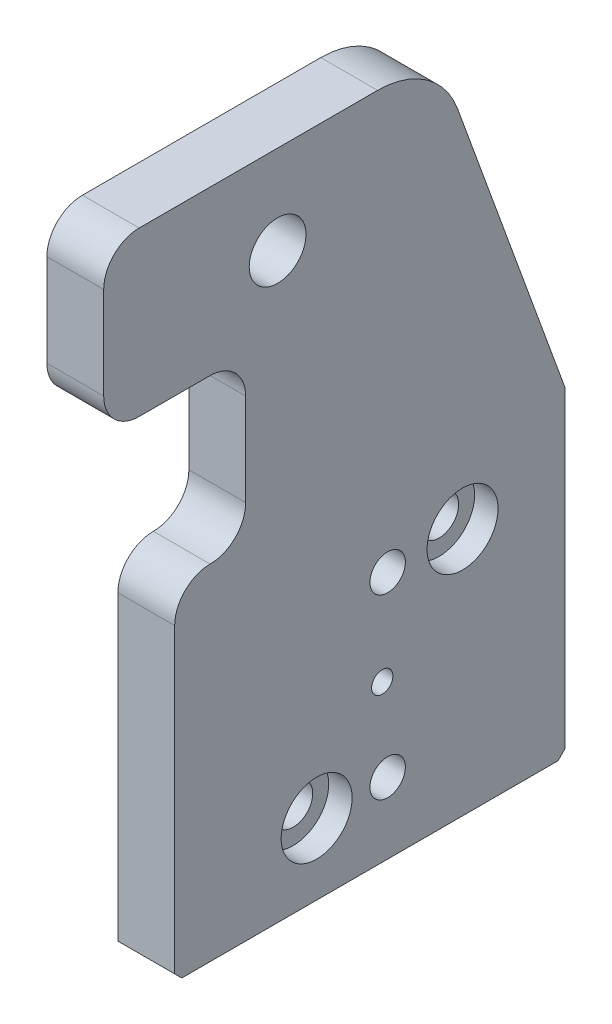
SolidWorks part; units mm, degrees
ref_plane "Front Plane" through (0, 0, 0) normal (0, 0, 1) x (1, 0, 0)
ref_plane "Top Plane" through (0, 0, 0) normal (0, 1, 0) x (1, 0, 0)
ref_plane "Right Plane" through (0, 0, 0) normal (1, 0, 0) x (0, 0, -1)
sketch "Sketch1" plane through (0, 0, 0) normal (1, 0, 0) x (0, 0, -1)
  line L0 (65, 45) -> (46.9835, 94.5)
  line L1 (0, 0) -> (65, 0)
  line L2 (0, 0) -> (0, 94.5)
  line L3 (0, 94.5) -> (65, 94.5)
  line L4 (65, 0) -> (65, 94.5)
  line L5 (0, 0) -> (65, 94.5) construction
  line L6 (0, 94.5) -> (65, 0) construction
  line L7 (0, 71.5) -> (20, 71.5)
  line L8 (20, 71.5) -> (20, 48.5)
  line L9 (20, 48.5) -> (10, 48.5)
  line L10 (10, 48.5) -> (10, 0)
  point P4 (32.5, 47.25)
  dimension "D1" = 65
  dimension "D2" = 94.5
  dimension "D3" = 45
  dimension "D4" = 20
  dimension "D5" = 55
  dimension "D6" = 48.5
extrude "Boss-Extrude1" add sketch "Sketch1" along normal blind 8 contours L9 L10 L1 L4 L0 L3 L2 L7 L8 region at (0, 45.4776, -34.9988)
fillet "Fillet1" radius 12 1 edges at (4, 94.5, -46.9835)
fillet "Fillet2" radius 5 1 edges at (4, 94.5, 0)
fillet "Fillet3" radius 5 4 edges at (4, 48.5, -10) (4, 48.5, -20) (4, 71.5, -20) (4, 71.5, 0)
chamfer "Chamfer2" distance 1 angle 45 2 edges at (4, 0, -10) (4, 0, -65)
sketch "Sketch5" plane through (0, 0, 0) normal (1, 0, 0) x (0, 0, -1)
  line L0 (0, 82) -> (24.5, 82) construction
  line L1 (0, 76.5) -> (0, 89.5) construction
  line L2 (24.5, 82) -> (24.5, 94.5) construction
  line L3 (5, 94.5) -> (38.581, 94.5) construction
  dimension "D1" = 12.5
  dimension "D2" = 24.5
sketch "Sketch8" plane through (0, 0, 0) normal (1, 0, 0) x (0, 0, -1)
  line L0 (10, 10.0011) -> (65, 10.0011) construction
  line L1 (10, 43.5) -> (10, 1) construction
  line L2 (65, 1) -> (65, 45) construction
  line L3 (11, 0) -> (64, 0) construction
  line L4 (30, 0) -> (30, 20.0022) construction
  line L5 (40, 0) -> (40, 20.0022) construction
  line L6 (10, 22) -> (65, 22) construction
  line L7 (10, 35) -> (65, 35) construction
  line L8 (40, 37.5876) -> (40, 32.4124) construction
  line L9 (50.5528, 37.5876) -> (50.5528, 32.4124) construction
  line L10 (39, 24.8044) -> (39, 19.1956) construction
  point P22 (40, 35)
  point P23 (50.5528, 35)
  point P28 (39, 22)
  point P31 (30, 10.0011)
  point P35 (40, 10.0011)
  dimension "D1" = 20
  dimension "D2" = 30
  dimension "D3" = 29
  dimension "D4" = 22
  dimension "D5" = 10.0011
  dimension "D6" = 35
hole_wizard "Ø5.0mm Dowel Hole3" positions "Sketch11" profile "Sketch12" hole size "Ø5.0" standard "ANSI Metric" end condition through all
sketch "Sketch11" plane through (0, 0, 0) normal (1, 0, 0) x (0, 0, -1)
  line L0 (40, 37.5876) -> (40, 32.4124) construction
  line L1 (40, 0) -> (40, 20.0022) construction
  point P0 (40, 35)
  point P4 (40, 10.0011)
sketch "Sketch12" plane through (0, 35, -40) normal (0, 1, 0) x (0, 0, 1)
  line L0 (0, 0) -> (0, 8)
  line L1 (0, 8) -> (2.5, 8)
  line L2 (2.5, 8) -> (2.5, 0)
  line L5 (2.5, 0) -> (0, 0)
  line L11 (0, -6.35) -> (0, 107.95) construction
  dimension "Thru Hole Dia." = 5
  dimension "Thru Hole Depth" = 8
hole_wizard "Ø3.0mm Dowel Hole1" positions "Sketch13" profile "Sketch14" hole size "Ø3.0" standard "ANSI Metric" end condition through all
sketch "Sketch13" plane through (0, 0, 0) normal (1, 0, 0) x (0, 0, -1)
  line L0 (10, 22) -> (65, 22) construction
  point P0 (39.2397, 22)
sketch "Sketch14" plane through (0, 22, -39.2397) normal (0, 1, 0) x (0, 0, 1)
  line L0 (0, 0) -> (0, 8)
  line L1 (0, 8) -> (1.5, 8)
  line L2 (1.5, 8) -> (1.5, 0)
  line L5 (1.5, 0) -> (0, 0)
  line L11 (0, -6.35) -> (0, 107.95) construction
  dimension "Thru Hole Dia." = 3
  dimension "Thru Hole Depth" = 8
ref_plane "Plane2" through (8, 0, 0) normal (1, 0, 0) x (0, 0, -1)
hole_wizard "CBORE for M5 Cheese Head Screw5" positions "Sketch30" profile "Sketch31" counterbore size "M5" standard "DIN" end condition through all
sketch "Sketch30" plane through (8, 0, 0) normal (1, 0, 0) x (0, 0, -1)
  line L0 (30, 0) -> (30, 20.0022) construction
  point P0 (30, 10.0011)
sketch "Sketch31" plane through (8, 10.0011, -30) normal (0, 1, 0) x (0, 0, -1)
  line L0 (0, 0) -> (0, 8)
  line L1 (0, 8) -> (2.75, 8)
  line L3 (2.75, 8) -> (2.75, 3.3)
  line L4 (2.75, 3.3) -> (5, 3.3)
  line L5 (5, 3.3) -> (5, 0)
  line L7 (5, 0) -> (0, 0)
  line L11 (0, -6.35) -> (0, 107.95) construction
  dimension "Thru Hole Dia." = 5.5
  dimension "Thru Hole Depth" = 8
  dimension "C'Bore Dia." = 10
  dimension "C'Bore Depth" = 3.3
hole_wizard "CBORE for M5 Cheese Head Screw6" positions "Sketch32" profile "Sketch33" counterbore size "M5" standard "DIN" end condition through all
sketch "Sketch32" plane through (8, 0, 0) normal (1, 0, 0) x (0, 0, -1)
  line L0 (50.5528, 37.5876) -> (50.5528, 32.4124) construction
  point P0 (50.5528, 35)
sketch "Sketch33" plane through (8, 35, -50.5528) normal (0, 1, 0) x (0, 0, -1)
  line L0 (0, 0) -> (0, 8)
  line L1 (0, 8) -> (2.75, 8)
  line L3 (2.75, 8) -> (2.75, 3.3)
  line L4 (2.75, 3.3) -> (5, 3.3)
  line L5 (5, 3.3) -> (5, 0)
  line L7 (5, 0) -> (0, 0)
  line L11 (0, -6.35) -> (0, 107.95) construction
  dimension "Thru Hole Dia." = 5.5
  dimension "Thru Hole Depth" = 8
  dimension "C'Bore Dia." = 10
  dimension "C'Bore Depth" = 3.3
hole_wizard "Ø8.0mm Dowel Hole3" positions "Sketch35" profile "Sketch36" hole size "Ø8.0" standard "ANSI Metric" end condition through all
sketch "Sketch35" plane through (0, 0, 0) normal (1, 0, 0) x (0, 0, -1)
  point P0 (24.5, 82)
sketch "Sketch36" plane through (0, 82, -24.5) normal (0, 1, 0) x (0, 0, 1)
  line L0 (0, 0) -> (0, 8)
  line L1 (0, 8) -> (4, 8)
  line L2 (4, 8) -> (4, 0)
  line L5 (4, 0) -> (0, 0)
  line L11 (0, -6.35) -> (0, 107.95) construction
  dimension "Thru Hole Dia." = 8
  dimension "Thru Hole Depth" = 8
